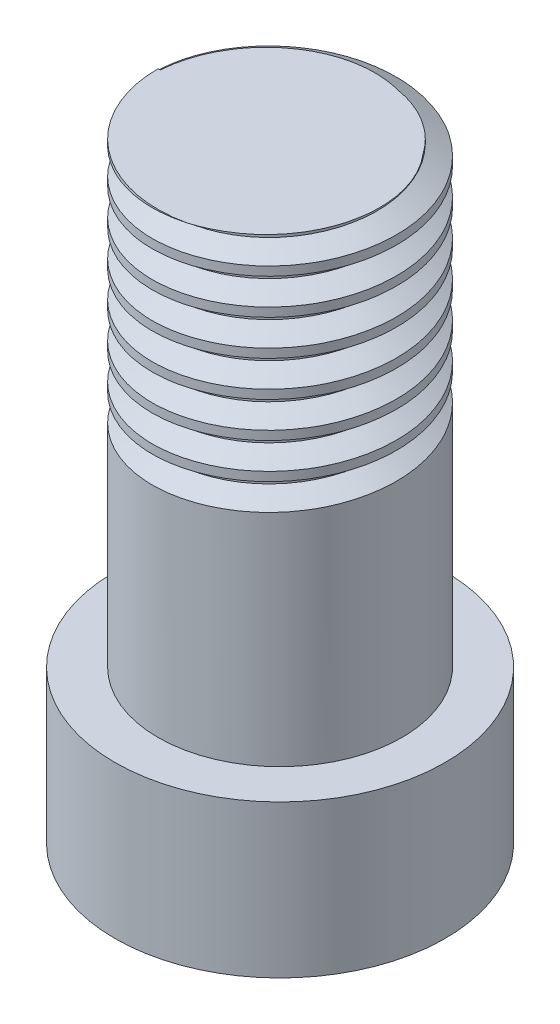
SolidWorks part; units mm, degrees
ref_plane "정면" through (0, 0, 0) normal (0, 0, 1) x (1, 0, 0)
ref_plane "윗면" through (0, 0, 0) normal (0, 1, 0) x (1, 0, 0)
ref_plane "우측면" through (0, 0, 0) normal (1, 0, 0) x (0, 0, -1)
sketch "스케치1" plane through (0, 0, 0) normal (0, 1, 0) x (1, 0, 0)
  circle A0 centre (0, 0) radius 3.25
  circle A1 centre (0, 0) radius 2.4
  dimension "D1" = 6.5
  dimension "D2" = 4.8
extrude "보스-돌출4" add sketch "스케치1" along normal blind 12 contours A1
extrude "보스-돌출5" add sketch "스케치1<6>" along normal blind 3
sketch "스케치1<6>" plane through (0, 0, 0) normal (0, 1, 0) x (1, 0, 0) same geometry as "스케치1"
ref_plane "평면6" through (0, 12.5, 0) normal (0, 1, 0) x (1, 0, 0)
thread "나사산6" pitch 0.7 method cut profile "나사산 프로파일7" start angle 0, offset 0, length 5, pitch 0.7, diameter 4.8
ref_plane "평면8" through (-2.4, 12.5, 0) normal (0, 0, -1) x (1, 0, 0)
sketch "나사산 프로파일7" plane through (-2.4, 12.5, 0) normal (0, 0, -1) x (1, 0, 0)
  line L0 (0, 0) -> (0, 0.7) construction
  line L1 (0, 0) -> (0.3789, 0.2187)
  line L2 (0.3789, 0.2187) -> (0.3789, 0.3062)
  line L3 (0.3789, 0.3062) -> (0, 0.525)
  line L4 (0.3789, 0.2625) -> (0, 0.2625) construction
  line L11 (0, 0) -> (0, 0.525)
  point P2 (0, 0)
  dimension "Pitch" = 0.7
  dimension "Profile_Angle" = 60
  dimension "Profile_Land" = 0.0875
  dimension "Profile_Height" = 0.3789
